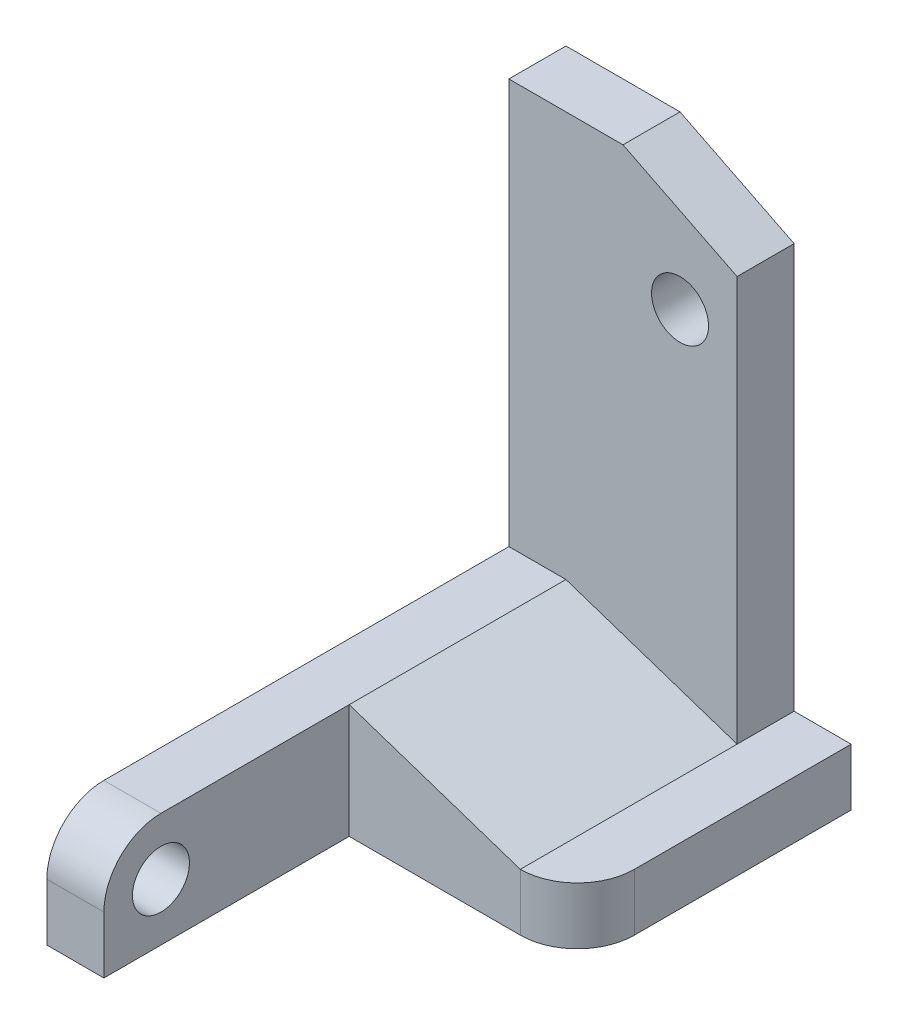
SolidWorks part; units mm, degrees
ref_plane "Front Plane" through (0, 0, 0) normal (0, 0, 1) x (1, 0, 0)
ref_plane "Top Plane" through (0, 0, 0) normal (0, 1, 0) x (1, 0, 0)
ref_plane "Right Plane" through (0, 0, 0) normal (1, 0, 0) x (0, 0, -1)
sketch "Sketch1" plane through (0, 0, 0) normal (0, 0, 1) x (1, 0, 0)
  line L0 (0, 0) -> (0, 2311.4)
  line L1 (0, 2311.4) -> (508, 2311.4)
  line L2 (508, 2311.4) -> (1016, 2057.4)
  line L3 (1016, 2057.4) -> (1016, 254)
  line L4 (1016, 254) -> (1270, 254)
  line L5 (1270, 254) -> (1270, 0)
  line L6 (1270, 0) -> (0, 0)
  line L7 (1016, 254) -> (254, 508)
  line L8 (254, 508) -> (254, 0)
  line L9 (254, 0) -> (254, 508)
  line L10 (254, 508) -> (0, 508)
  circle A0 centre (762, 1803.4) radius 127
  point P13 (0, 0)
  dimension "D7" = 254
  dimension "D1" = 508
  dimension "D2" = 2311.4
  dimension "D3" = 1803.4
  dimension "D4" = 254
  dimension "D5" = 508
  dimension "D6" = 1270
  dimension "D8" = 254
  dimension "D9" = 254
  dimension "D10" = 254
  dimension "D11" = 254
extrude "Boss-Extrude1" add sketch "Sketch1" along normal blind 254 contours L10 L7 L3 L2 L1 L0 A0 region at (502.4101, 1317.0153, 0)
extrude "Boss-Extrude2" add sketch "Sketch1<3>" along normal blind 1219.2 contours L7 L8 L6 L5 L4 region at (692.7273, 184.7273, 0)
sketch "Sketch1<3>" plane through (0, 0, 0) normal (0, 0, 1) x (1, 0, 0) same geometry as "Sketch1"
fillet "Fillet1" radius 254 1 edges at (1270, 127, 1219.2)
sketch "Sketch2" plane through (254, 0, 0) normal (-1, 0, 0) x (0, 0, 1)
  line L0 (0, 0) -> (2311.4, 0)
  line L1 (0, 0) -> (0, 508)
  line L2 (0, 508) -> (2311.4, 508)
  line L3 (2311.4, 508) -> (2311.4, 0)
  circle A0 centre (2057.4, 254) radius 127
  dimension "D2" = 254
  dimension "D1" = 2311.4
  dimension "D3" = 254
  dimension "D4" = 254
extrude "Boss-Extrude3" add sketch "Sketch2" along normal blind 254
fillet "Fillet2" radius 254 1 edges at (127, 508, 2311.4)
